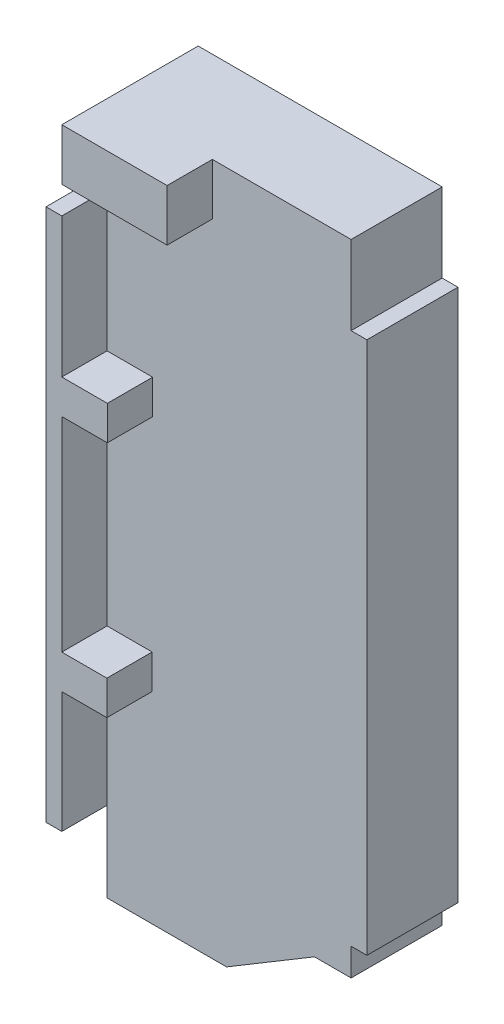
SolidWorks part; units mm, degrees
ref_plane "Front Plane" through (0, 0, 0) normal (0, 0, 1) x (1, 0, 0)
ref_plane "Top Plane" through (0, 0, 0) normal (0, 1, 0) x (1, 0, 0)
ref_plane "Right Plane" through (0, 0, 0) normal (1, 0, 0) x (0, 0, -1)
sketch "Sketch2" plane through (0, 0, 0) normal (0, 0, 1) x (1, 0, 0)
  line L0 (32.2123, 127) -> (32.2123, 88.2904) construction
  line L1 (-25.4, 384.175) -> (92.329, 384.175)
  line L2 (-25.4, 384.175) -> (-25.4, 127)
  line L3 (-25.4, 127) -> (92.329, 127)
  line L4 (92.329, 384.175) -> (92.329, 127)
  line L5 (-25.4, 384.175) -> (92.329, 384.175)
  line L6 (-25.4, 384.175) -> (-25.4, 422.275)
  line L7 (-25.4, 422.275) -> (92.329, 422.275)
  line L8 (92.329, 384.175) -> (92.329, 422.275)
  line L9 (-25.4, 422.275) -> (25.4, 422.275)
  line L10 (-25.4, 422.275) -> (-25.4, 397.3703)
  line L11 (-25.4, 397.3703) -> (25.4, 397.3703)
  line L12 (25.4, 422.275) -> (25.4, 397.3703)
  line L13 (-25.4, 127) -> (92.329, 127)
  line L14 (-25.4, 127) -> (-25.4, 88.2904)
  line L15 (-25.4, 88.2904) -> (92.329, 88.2904)
  line L16 (92.329, 127) -> (92.329, 88.2904)
  line L17 (92.329, 113.7158) -> (-25.4, 113.7158) construction
  line L18 (74.6506, 127) -> (74.6506, 88.2904) construction
  line L19 (92.329, 113.7158) -> (74.6506, 113.7158)
  line L20 (74.6506, 113.7158) -> (32.2123, 88.2904)
  line L22 (-25.4, 384.175) -> (-33.02, 384.175)
  line L23 (-25.4, 384.175) -> (-25.4, 127)
  line L24 (-25.4, 127) -> (-33.02, 127)
  line L25 (-33.02, 384.175) -> (-33.02, 127)
  line L26 (92.329, 384.175) -> (99.949, 384.175)
  line L27 (92.329, 384.175) -> (92.329, 127)
  line L28 (92.329, 127) -> (99.949, 127)
  line L29 (99.949, 384.175) -> (99.949, 127)
  line L30 (-25.4, 201.93) -> (-3.6576, 201.93)
  line L31 (-25.4, 201.93) -> (-25.4, 185.42)
  line L32 (-25.4, 185.42) -> (-3.6576, 185.42)
  line L33 (-3.6576, 201.93) -> (-3.6576, 185.42)
  line L34 (-25.4, 316.865) -> (-3.429, 316.865)
  line L35 (-25.4, 316.865) -> (-25.4, 300.355)
  line L36 (-25.4, 300.355) -> (-3.429, 300.355)
  line L37 (-3.429, 316.865) -> (-3.429, 300.355)
  dimension "D1" = 257.175
  dimension "D2" = 117.729
  dimension "D3" = 38.1
  dimension "D4" = 50.8
  dimension "D5" = 24.9047
  dimension "D6" = 127
  dimension "D7" = 25.4
  dimension "D8" = 38.7096
  dimension "D9" = 57.6123
  dimension "D10" = 13.2842
  dimension "D11" = 17.6784
  dimension "D12" = 7.62
  dimension "D13" = 7.62
  dimension "D14" = 58.42
  dimension "D15" = 21.7424
  dimension "D16" = 16.51
  dimension "D17" = 16.51
  dimension "D18" = 67.31
  dimension "D19" = 21.971
extrude "Boss-Extrude1" add sketch "Sketch2" against normal blind 43.942 contours L12 L7 L6 L11 | L7 L12 L11 L6 L1 L8 | L22 L25 L24 L2 L23 | L34 L37 L36 L2 L30 L33 L32 L3 L4 L1 | L37 L34 L23 L36 | L33 L30 L23 L32 | L29 L26 L4 L28 | L20 L19 L16 L3 L14 L15 region at (46.6116, 400.633, 0) region at (34.635, 255.6887, 0) region at (-29.21, 255.5875, 0) region at (96.139, 255.5875, 0) region at (-14.4145, 308.61, 0) region at (0, 409.8227, 0) region at (23.0747, 110.1268, 0) region at (-14.5288, 193.675, 0)
extrude "Boss-Extrude3" add sketch "Sketch2<6>" along normal blind 21.844 contours L22 L25 L24 L2 L23 | L37 L34 L23 L36 | L33 L30 L23 L32 | L12 L7 L6 L11 region at (-29.21, 255.5875, 0) region at (-14.4145, 308.61, 0) region at (0, 409.8227, 0) region at (-14.5288, 193.675, 0)
sketch "Sketch2<6>" plane through (0, 0, 0) normal (0, 0, 1) x (1, 0, 0) same geometry as "Sketch2"
